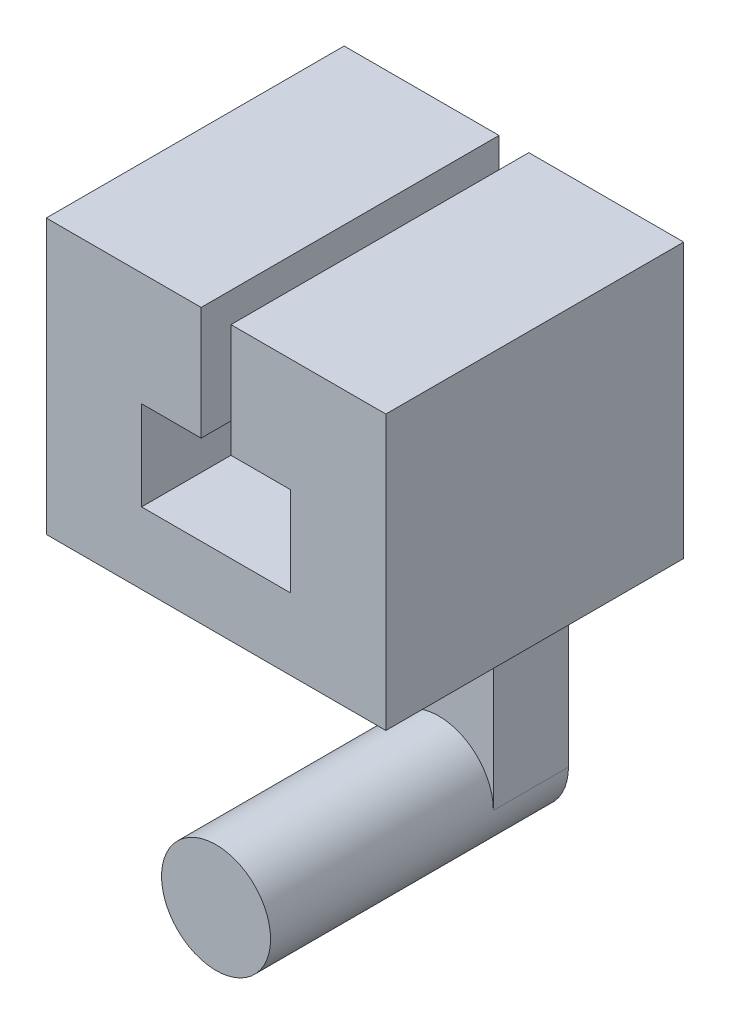
SolidWorks part; units mm, degrees
ref_plane "Front Plane" through (0, 0, 0) normal (0, 0, 1) x (1, 0, 0)
ref_plane "Top Plane" through (0, 0, 0) normal (0, 1, 0) x (1, 0, 0)
ref_plane "Right Plane" through (0, 0, 0) normal (1, 0, 0) x (0, 0, -1)
sketch "Sketch1" plane through (0, 0, 0) normal (0, 0, 1) x (1, 0, 0)
  circle A0 centre (0, 0) radius 23.241
  dimension "D1" = 46.482
extrude "ftA" add sketch "Sketch1" against normal blind 127 contours A0
sketch "Sketch2" plane through (0, 0, -127) normal (0, 0, -1) x (-1, 0, 0)
  line L1 (-23.241, 0) -> (23.241, 0)
  line L2 (-23.241, 0) -> (-23.241, 101.6)
  line L3 (-23.241, 101.6) -> (23.241, 101.6)
  line L4 (23.241, 0) -> (23.241, 101.6)
  circle A0 centre (0, 0) radius 23.241 construction
  dimension "D1" = 46.482
  dimension "D2" = 101.6
extrude "ftB" add sketch "Sketch2" against normal blind 32.004 separate body
sketch "Sketch3" plane through (0, 0, -127) normal (0, 0, -1) x (-1, 0, 0)
  line L0 (-23.241, 101.6) -> (-31.75, 101.6)
  line L9 (-31.75, 101.6) -> (-31.75, 132.08)
  line L10 (-31.75, 132.08) -> (31.75, 132.08)
  line L11 (31.75, 132.08) -> (31.75, 101.6)
  line L12 (31.75, 101.6) -> (23.241, 101.6)
  line L13 (23.241, 101.6) -> (-23.241, 101.6)
  dimension "D1" = 63.5
  dimension "D2" = 30.48
extrude "ftC" add sketch "Sketch3" against normal blind 127 contours L13 L0 L9 L10 L11 L12
sketch "Sketch4" plane through (0, 0, 0) normal (0, 0, 1) x (1, 0, 0)
  line L9 (-31.75, 132.08) -> (-72.39, 132.08)
  line L10 (-31.75, 132.08) -> (-31.75, 170.18)
  line L11 (-31.75, 170.18) -> (-72.39, 170.18)
  line L12 (-72.39, 132.08) -> (-72.39, 170.18)
  line L13 (31.75, 132.08) -> (72.39, 132.08)
  line L14 (31.75, 132.08) -> (31.75, 170.18)
  line L15 (31.75, 170.18) -> (72.39, 170.18)
  line L16 (72.39, 132.08) -> (72.39, 170.18)
  point P10 (0, 0)
  point P11 (0, 0)
  point P14 (0, 0)
  dimension "D1" = 40.64
  dimension "D2" = 38.1
extrude "ftD1" add sketch "Sketch4" against normal blind 127 separate body contours L15 L16 L13 L14
extrude "ftD2" add sketch "Sketch4<5>" against normal blind 127
sketch "Sketch4<5>" plane through (0, 0, 0) normal (0, 0, 1) x (1, 0, 0) same geometry as "Sketch4"
sketch "Sketch5" plane through (0, 0, 0) normal (0, 0, 1) x (1, 0, 0)
  line L1 (-31.75, 170.18) -> (-6.35, 170.18)
  line L2 (-31.75, 170.18) -> (-31.75, 218.44)
  line L3 (-31.75, 218.44) -> (-6.35, 218.44)
  line L4 (-6.35, 170.18) -> (-6.35, 218.44)
  line L5 (31.75, 170.18) -> (6.35, 170.18)
  line L6 (31.75, 170.18) -> (31.75, 218.44)
  line L7 (31.75, 218.44) -> (6.35, 218.44)
  line L8 (6.35, 170.18) -> (6.35, 218.44)
  dimension "D1" = 48.26
  dimension "D2" = 25.4
extrude "ftE" add sketch "Sketch5" against normal blind 127 separate body
sketch "Sketch6" plane through (0, 0, 0) normal (0, 0, 1) x (1, 0, 0)
  line L0 (-31.75, 101.6) -> (31.75, 101.6) construction
  line L5 (31.75, 218.44) -> (72.39, 218.44)
  line L6 (31.75, 218.44) -> (31.75, 170.18)
  line L7 (31.75, 170.18) -> (72.39, 170.18)
  line L8 (72.39, 218.44) -> (72.39, 170.18)
  line L13 (-31.75, 218.44) -> (-72.39, 218.44)
  line L14 (-31.75, 218.44) -> (-31.75, 170.18)
  line L15 (-31.75, 170.18) -> (-72.39, 170.18)
  line L16 (-72.39, 218.44) -> (-72.39, 170.18)
  line L17 (-72.39, 132.08) -> (-31.75, 132.08)
  line L18 (-72.39, 132.08) -> (-72.39, 101.6)
  line L19 (-72.39, 101.6) -> (-31.75, 101.6)
  line L20 (-31.75, 132.08) -> (-31.75, 101.6)
  line L21 (31.75, 101.6) -> (72.39, 101.6)
  line L22 (31.75, 101.6) -> (31.75, 132.08)
  line L23 (31.75, 132.08) -> (72.39, 132.08)
  line L24 (72.39, 101.6) -> (72.39, 132.08)
extrude "Filler" add sketch "Sketch6" against normal blind 127
equation "\"F\"= 600'Applied force"
equation "\"Yst\"= 39885.32'Yield strength"
equation "\"Sf\"= 4'Safety factor"
equation "\"def\"= .005'Deflection"
equation "\"Lst\"= 5'Length of strap"
equation "\"E\"= 10007604'Modulus of elasticity"
equation "\"Dst\"= ( ( \"F\" * \"Lst\" * \"Sf\" * 32 * 2 ) / ( \"Yst\" * 3.14159 ) ) ^ ( 1 / 3 )'Driven diameter of feauture A"
equation "\"Lftb\"= 4'Chosen length of feature B"
equation "\"hftb\"= ( ( \"F\" * \"Lftb\" * \"Sf\" * 6 * 2 ) / ( \"Dst\" * \"Yst\" ) ) ^ ( 1 / 2 )'Driven height of feature B"
equation "\"Bftc\"= 2.5'Base of feature C, from T-beam dim"
equation "\"hftc\"= ( ( \"F\" * \"Lst\" * \"Sf\" * 2 * 6 ) / ( \"Bftc\" * \"Yst\" ) ) ^ ( 1 / 2 )'Driven height of feature C"
equation "\"hftd\"= 1.5'Chosen height of feature D"
equation "\"cftd\"= \"hftd\" / 2'Neutral axis of feature D (distance)"
equation "\"bftd\"= ( \"F\" * \"Lst\" * \"cftd\" * \"Sf\" * 2 * 12 ) / ( \"Yst\" * ( \"hftd\" ^ 3 ) )'Driven base of feature D"
equation "\"bfte\"= 1'Base of feature E, from T-beam dim"
equation "\"hfte\"= ( ( \"F\" * \"Lst\" * \"Sf\" * 6 * 2 ) / ( \"Yst\" * \"bfte\" ) ) ^ ( 1 / 2 )'Driven height of feature E"
equation "\"hlink\"= 6'Chosen height of link"
equation "\"blink\"= 2.25'Chosen base of link"
equation "\"clink\"= 3'Neutral axis of link (distance)"
equation "\"tlink\"= ( \"F\" * \"hlink\" * \"clink\" * \"Sf\" * 12 * 2 ) / ( \"Yst\" * ( \"hlink\" ^ 3 ) )'Driven thickness of link"
